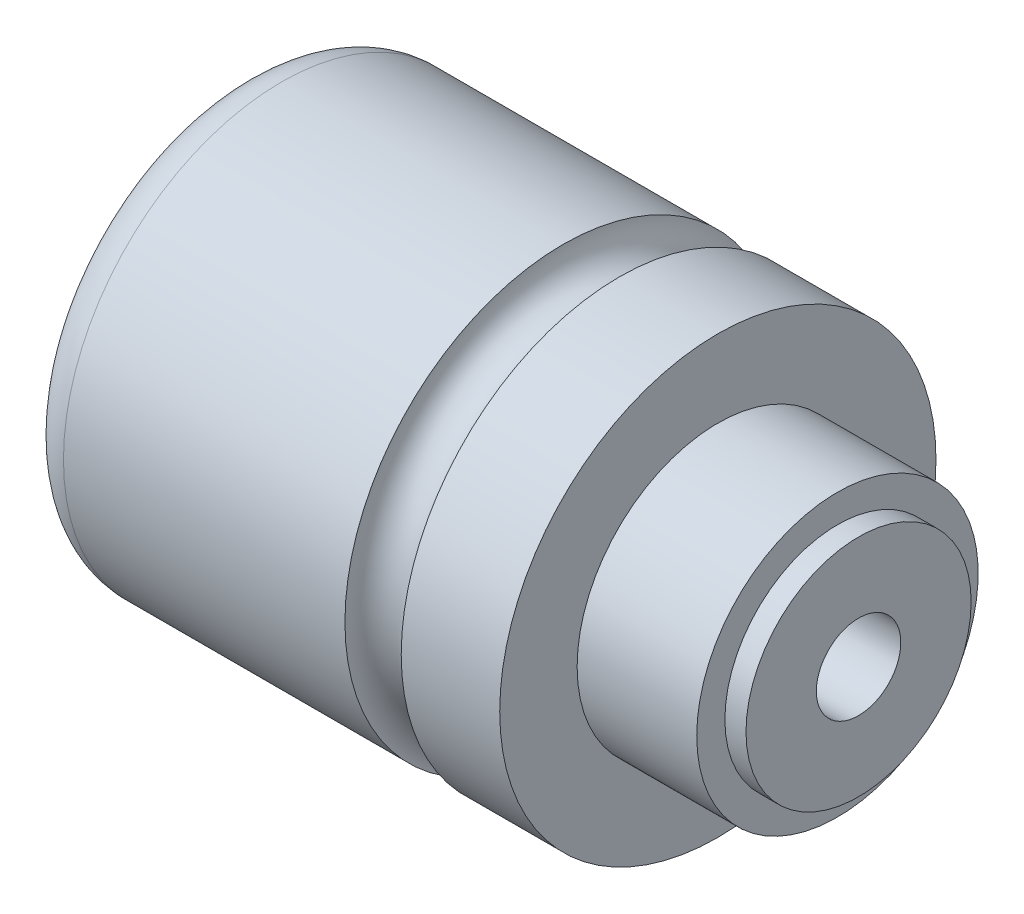
SolidWorks part; units mm, degrees
ref_plane "Front Plane" through (0, 0, 0) normal (0, 0, 1) x (1, 0, 0)
ref_plane "Top Plane" through (0, 0, 0) normal (0, 1, 0) x (1, 0, 0)
ref_plane "Right Plane" through (0, 0, 0) normal (1, 0, 0) x (0, 0, -1)
sketch "Sketch1" plane through (0, 0, 0) normal (0, 0, 1) x (1, 0, 0)
  line L0 (-44, 0) -> (44, 0) construction
  line L1 (44, 6) -> (44, 16)
  line L2 (44, 16) -> (41, 16)
  line L3 (41, 16) -> (41, 20)
  line L4 (41, 20) -> (24, 20)
  line L5 (24, 20) -> (24, 31)
  line L6 (24, 31) -> (10, 31)
  line L7 (-44, 31) -> (-44, 25)
  line L8 (-44, 25) -> (-42.5, 25)
  line L9 (-42.5, 25) -> (-42.5, 16)
  line L10 (-42.5, 16) -> (-32, 16)
  line L11 (-32, 16) -> (-32, 12.5)
  line L12 (-32, 12.5) -> (-29, 12.5)
  line L13 (-29, 12.5) -> (-29, 20.5)
  line L14 (-29, 20.5) -> (-22, 20.5)
  line L15 (-22, 20.5) -> (-22, 16)
  line L16 (-22, 16) -> (-14, 16)
  line L17 (-14, 16) -> (-14, 6)
  line L18 (-14, 6) -> (44, 6)
  line L19 (2, 31) -> (-44, 31)
  arc A0 (2, 31) -> (10, 31) centre (6, 31) ccw
  dimension "D17" = 8
  dimension "D20" = 16
  dimension "D1" = 88
  dimension "D2" = 16
  dimension "D3" = 3
  dimension "D4" = 20
  dimension "D5" = 25
  dimension "D6" = 31
  dimension "D7" = 1.5
  dimension "D8" = 9
  dimension "D9" = 12
  dimension "D10" = 3.5
  dimension "D11" = 3
  dimension "D12" = 8
  dimension "D13" = 22
  dimension "D14" = 8
  dimension "D15" = 10
  dimension "D16" = 68
  dimension "D18" = 50
  dimension "D19" = 20
  dimension "D21" = 20.5
revolve "Revolve1" add sketch "Sketch1" angle 360 about L0
fillet "Fillet3" radius 6 1 edges at (-44, 0, 31)
